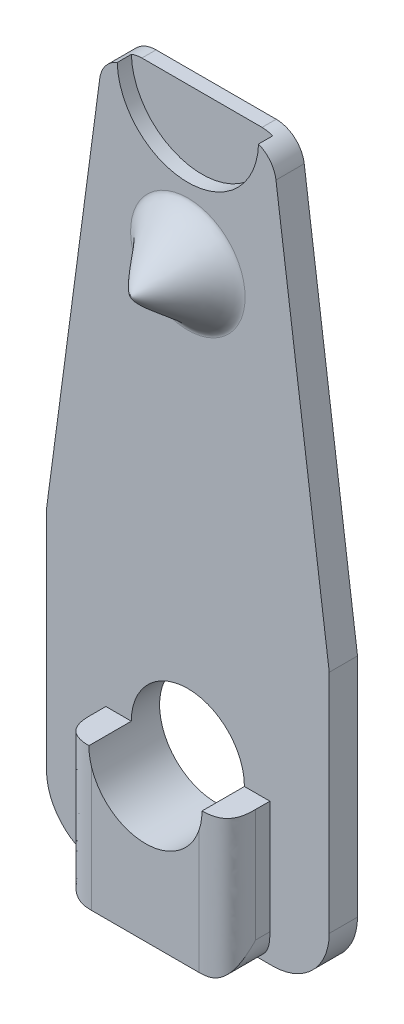
SolidWorks part; units mm, degrees
material "Maple"
ref_plane "Wasteboard" through (0, 0, 0) normal (0, 0, 1) x (1, 0, 0)
ref_plane "Left-Right" through (0, 0, 0) normal (0, 1, 0) x (1, 0, 0)
ref_plane "Front-Back" through (0, 0, 0) normal (1, 0, 0) x (0, 0, -1)
sketch "Sketch1" plane through (0, 0, 0) normal (0, 0, 1) x (1, 0, 0)
  line L0 (-3, -6.8603) -> (3, -6.8603)
  line L1 (5, -4.8603) -> (5, 3.1397)
  line L4 (2.1245, 18.1397) -> (-2.1245, 18.1397)
  line L5 (0, 0) -> (0, -2.6691) construction
  line L8 (-5, -4.8603) -> (-5, 3.1397)
  line L9 (-5, 3.1397) -> (-3.1157, 17.2719)
  line L10 (5, 3.1397) -> (3.1157, 17.2719)
  arc A0 (3, -6.8603) -> (5, -4.8603) centre (3, -4.8603) ccw
  arc A1 (-5, -4.8603) -> (-3, -6.8603) centre (-3, -4.8603) ccw
  arc A2 (3.1157, 17.2719) -> (2.1245, 18.1397) centre (2.1245, 17.1397) ccw
  arc A3 (-3.1157, 17.2719) -> (-2.1245, 18.1397) centre (-2.1245, 17.1397) cw
  point P11 (0, 18.1397)
  point P14 (0, -6.8603)
  dimension "D2" = 2
  dimension "D1" = 1
extrude "Boss-Extrude1" add sketch "Sketch1" along normal blind 1
sketch "Sketch3" plane through (0, 0, 1) normal (0, 0, 1) x (1, 0, 0)
  line L0 (-5, 3.1397) -> (5, 3.1397) construction
  line L1 (0, -6.8603) -> (0, 3.1397) construction
  line L2 (-3, -6.8603) -> (3, -6.8603) construction
  circle A0 centre (0, -1.8603) radius 2
  dimension "D1" = 4
sketch "Sketch4" plane through (0, 0, 1) normal (0, 0, 1) x (1, 0, 0)
  line L0 (-5, 3.1397) -> (5, 3.1397) construction
  line L1 (0, -1.8603) -> (0, -6.8603) construction
  line L2 (-3, -6.8603) -> (3, -6.8603) construction
  line L3 (2.9, -6.8603) -> (2.9, -1.8603)
  line L4 (2.9, -1.8603) -> (-2.9, -1.8603)
  line L5 (2.9, -6.8603) -> (-2.9, -6.8603)
  line L6 (-2.9, -6.8603) -> (-2.9, -1.8603)
  line L7 (0, 3.1397) -> (0, -6.8603) construction
  point P13 (0, -3.2284)
  dimension "D1" = 2.9
  dimension "D2" = 10
  dimension "D3" = 5
extrude "Boss-Extrude2" add sketch "Sketch4" along normal blind 1.5
extrude "Cut-Extrude2" cut sketch "Sketch3" against normal through all both and the other way through all
sketch "Sketch5" plane through (0, 0, 1) normal (0, 0, 1) x (1, 0, 0)
  line L0 (0, 18.1397) -> (0, 13.1397) construction
  line L1 (2.1245, 18.1397) -> (-2.1245, 18.1397) construction
  circle A0 centre (0, 13.1397) radius 2 construction
  point P6 (0, 0)
  point P7 (0, 0)
  dimension "D1" = 5
sketch3d "3DSketch4"
  line L0 (0, 15.1648, 1) -> (0, 13.1397, 1)
  line L7 (0, 13.1397, 1) -> (0, 13.1397, 4.0653) construction
  line L8 (0, 13.1397, 1) -> (0, 13.1397, 3)
  spline S0 degree 3 poles (0, 13.1397, 3) (-0.0469, 14.2264, 2.8641) (-0.4641, 14.6092, 1.3599) (0, 15.1648, 1) knots 0 0 0 0 1 1 1 1
  point P0 (0, 13.1397, 1)
  dimension "D1" = 2
ref_plane "Plane2" through (0, 0, 0) normal (-1, 0, 0) x (0, 0, 1)
sketch "Sketch10" plane through (0, 0, 0) normal (-1, 0, 0) x (0, 0, 1)
  line L0 (3, 13.1397) -> (1, 13.1397)
  line L1 (1, 13.1397) -> (1, 15.1648)
  spline S0 degree 3 poles (1, 15.1648) (1.0036, 14.7683) (2.9093, 13.5975) (3, 13.1397) knots 0 0 0 0 1 1 1 1
revolve "Revolve1" add sketch "Sketch10" angle 360 about L0
fillet "Fillet2" radius 1 4 edges at (2.9, -4.3603, 2.5) (-2.9, -4.3603, 2.5) (2.9, -6.8603, 1.75) (-2.9, -6.8603, 1.75) curvature continuous yes
sketch "Sketch11" plane through (0, 0, 1) normal (0, 0, 1) x (1, 0, 0)
  circle A0 centre (0, 18.1397) radius 2.5
  dimension "D1" = 5
extrude "Cut-Extrude4" cut sketch "Sketch11" against normal blind 0.5
